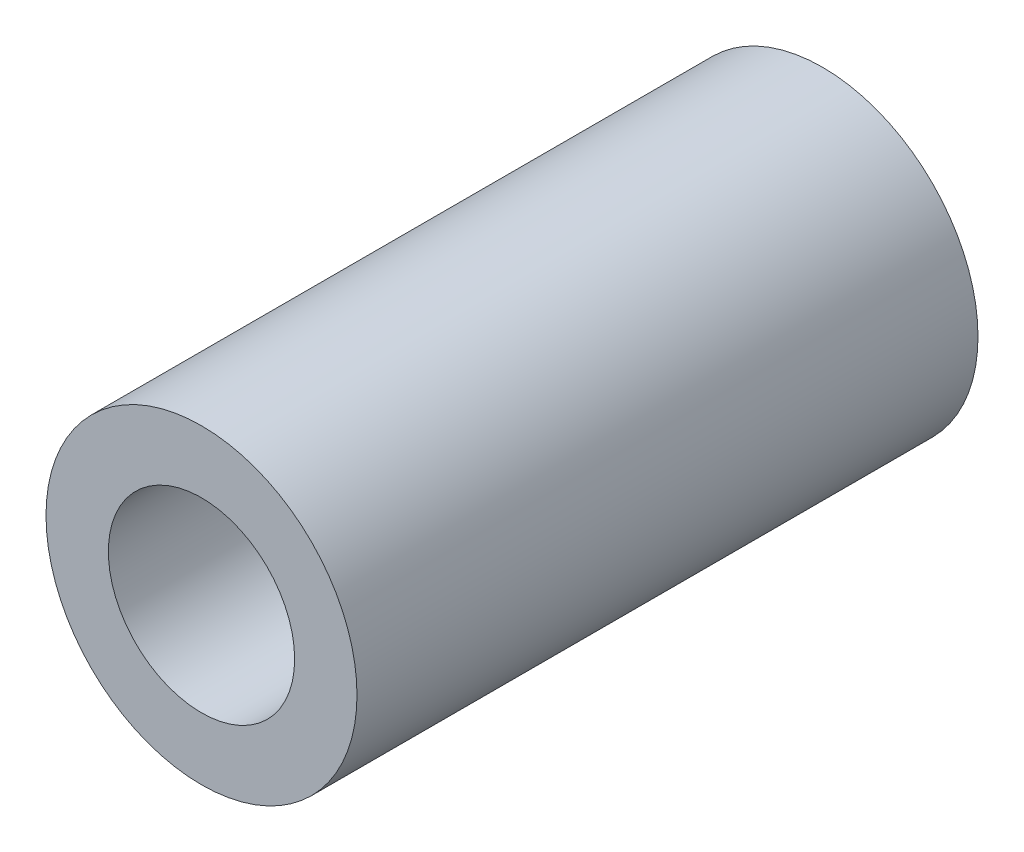
SolidWorks part; units mm, degrees
ref_plane "Front Plane" through (0, 0, 0) normal (0, 0, 1) x (1, 0, 0)
ref_plane "Top Plane" through (0, 0, 0) normal (0, 1, 0) x (1, 0, 0)
ref_plane "Right Plane" through (0, 0, 0) normal (1, 0, 0) x (0, 0, -1)
sketch "Sketch1" plane through (0, 0, 0) normal (0, 0, 1) x (1, 0, 0)
  circle A0 centre (0, 0) radius 7.9502
  circle A1 centre (0, 0) radius 4.7625
  dimension "OD" = 15.9004
  dimension "ID" = 9.525
sketch "Sketch2" plane through (0, 0, 0) normal (1, 0, 0) x (0, 0, -1)
  line L2 (15.875, 0) -> (-15.875, 0) construction
  line L4 (-15.875, -7.9502) -> (-15.875, 7.9502) construction
  line L5 (-15.875, -4.7625) -> (15.875, -4.7625)
  line L6 (15.875, 4.7625) -> (-15.875, 4.7625)
  line L7 (15.875, -7.9502) -> (15.875, 7.9502) construction
  line L8 (-15.875, 7.9502) -> (15.875, 7.9502) construction
  line L9 (-15.875, -7.9502) -> (15.875, -7.9502) construction
  line L10 (0, 7.9502) -> (0, -7.9502) construction
  line L11 (0, 4.7625) -> (0, -4.7625) construction
  point P4 (0, -4.7625)
  point P7 (0, 4.7625)
  point P8 (0, 0)
  point P12 (-15.875, 0)
  point P15 (15.875, 0)
  point P16 (0, -7.9502)
  point P17 (0, 7.9502)
  dimension "Length" = 31.75
sketch "Sketch5" plane through (0, 0, 0) normal (0, 0, 1) x (1, 0, 0)
  circle A1 centre (0, 0) radius 4.7625
  circle A2 centre (0, 0) radius 4.7625
  circle A3 centre (0, 0) radius 7.9502
  circle A4 centre (0, 0) radius 7.9502
  dimension "D1" = 0
  dimension "D2" = 0
extrude "Boss-Extrude1" add sketch "Sketch5" along normal up to vertex and the other way up to vertex up to point (0, 0, 15.875) other way up to point (0, 0, -15.875)
sketch "Sketch4" plane through (0, 0, 15.875) normal (0, 0, 1) x (1, 0, 0)
  line L0 (0, 0) -> (-3.3676, 3.3676)
  line L2 (0, -7.9502) -> (0, 7.9502) construction
  circle A1 centre (0, 0) radius 4.7625 construction
  dimension "D1" = 45
equation "\"D1\"= \"Length@Sketch2\""
